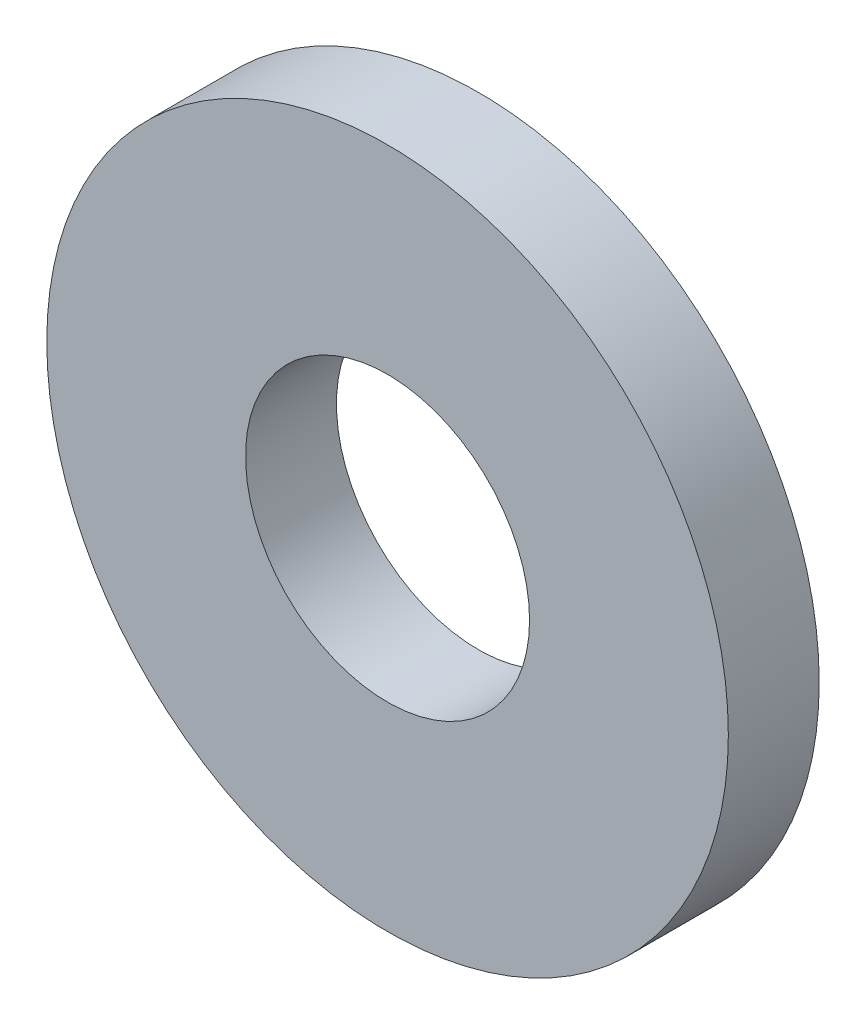
SolidWorks part; units mm, degrees
material "Alloy Steel"
ref_plane "Plane1" through (0, 0, 0) normal (0, 0, 1) x (1, 0, 0)
ref_plane "Plane2" through (0, 0, 0) normal (0, 1, 0) x (1, 0, 0)
ref_plane "Plane3" through (0, 0, 0) normal (1, 0, 0) x (0, 0, -1)
ref_axis "Axis1" through (-83.9706, 0, 0) along (1, 0, 0)
ref_axis "Axis2" through (0, 0, -0.0635) along (0, 0, 1)
ref_axis "Axis3" through (0, 5.2388, 0) along (0, -1, 0)
sketch "Sketch1" plane through (0, 0, 0) normal (0, 0, 1) x (1, 0, 0)
  circle A0 centre (0, 0) radius 1.9844
  circle A1 centre (0, 0) radius 4.7625
  dimension "D1" = 3.9688
  dimension "D2" = 9.525
extrude "Boss-Extrude1" add sketch "Sketch1" along normal blind 1.27
equation "\"id\"= 0.15625"
equation "\"od\"= 0.375"
equation "\"thk\"= 0.05"
equation "\"D1@Sketch1\" = \"id\""
equation "\"D2@Sketch1\" = \"od\""
equation "\"D1@Boss-Extrude1\" = \"thk\""
